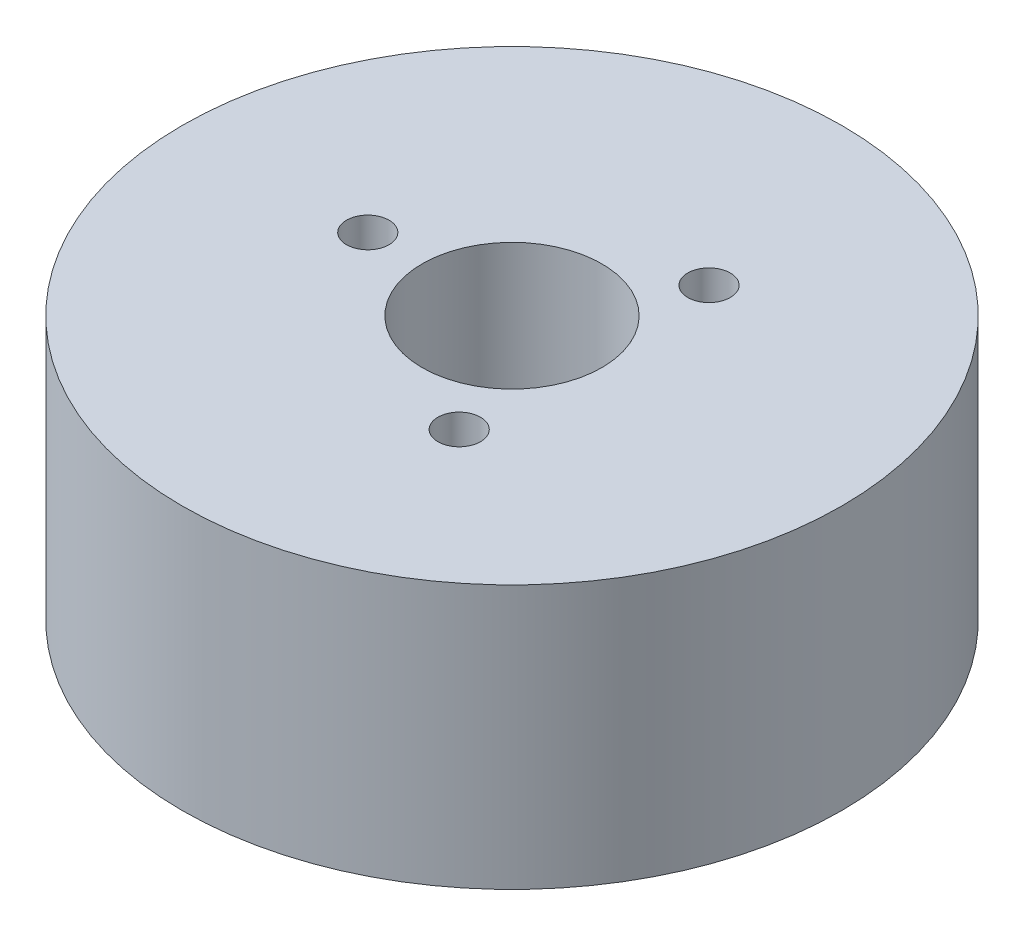
SolidWorks part; units mm, degrees
ref_plane "Front Plane" through (0, 0, 0) normal (0, 0, 1) x (1, 0, 0)
ref_plane "Top Plane" through (0, 0, 0) normal (0, 1, 0) x (1, 0, 0)
ref_plane "Right Plane" through (0, 0, 0) normal (1, 0, 0) x (0, 0, -1)
sketch "Sketch1" plane through (0, 0, 0) normal (0, 1, 0) x (1, 0, 0)
  circle A0 centre (0, 0) radius 27.5
  dimension "FLANGE_OD" = 55
extrude "Boss-Extrude1" add sketch "Sketch1" along normal blind 22
sketch "Sketch2" plane through (0, 0, 0) normal (0, 1, 0) x (1, 0, 0)
  circle A0 centre (0, 0) radius 7.5
  dimension "BORE_D" = 15
extrude "Cut-Extrude1" cut sketch "Sketch2" along normal through all
sketch "Sketch3" plane through (0, 22, 0) normal (0, 1, 0) x (1, 0, 0)
  circle A0 centre (0, 0) radius 12.029 construction
  circle A1 centre (-12.029, 0) radius 1.7753
  dimension "BOLT_D" = 3.5507
  dimension "BOLT_PCD" = 24.058
extrude "Cut-Extrude2" cut sketch "Sketch3" against normal blind 20.3874
pattern_circular "CirPattern1" count 3 over 360 about axis through (0, 0, 0) along (0, 1, 0) of "Cut-Extrude2"
